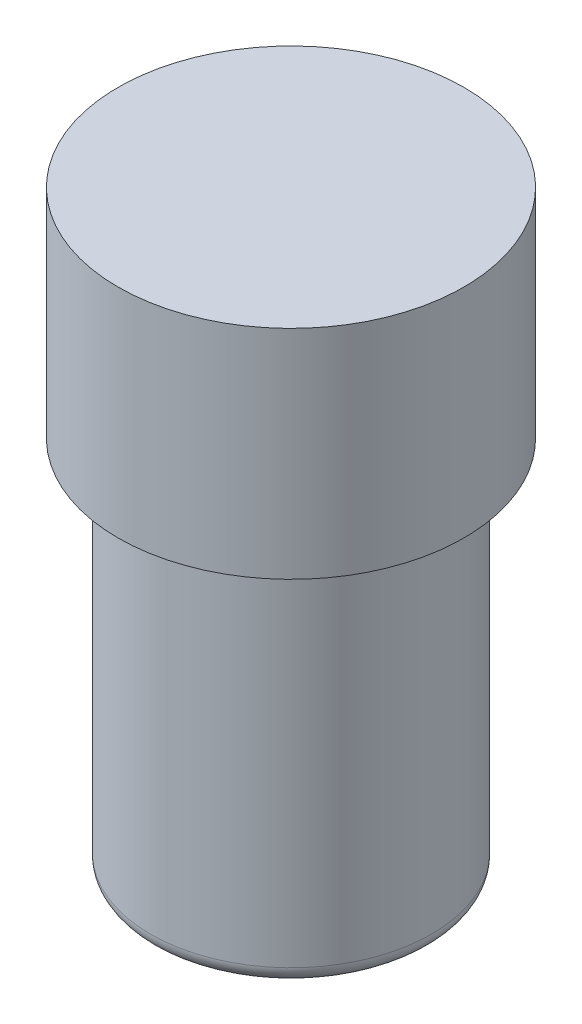
SolidWorks part; units mm, degrees
ref_plane "Front Plane" through (0, 0, 0) normal (0, 0, 1) x (1, 0, 0)
ref_plane "Top Plane" through (0, 0, 0) normal (0, 1, 0) x (1, 0, 0)
ref_plane "Right Plane" through (0, 0, 0) normal (1, 0, 0) x (0, 0, -1)
sketch "Sketch1" plane through (0, 0, 0) normal (0, 1, 0) x (1, 0, 0)
  circle A0 centre (0, 0) radius 5.0535
  circle A1 centre (0, 0) radius 4.1047
  dimension "D1" = 10.107
  dimension "D2" = 8.2094
extrude "Boss-Extrude1" add sketch "Sketch1" along normal blind 6.35 contours A1 | A0 A1 region at (-4.9106, 0, 0) region at (0, 0, 0)
extrude "Boss-Extrude2" add sketch "Sketch1<3>" against normal blind 11 contours A1 region at (0, 0, 0)
sketch "Sketch1<3>" plane through (0, 0, 0) normal (0, 1, 0) x (1, 0, 0) same geometry as "Sketch1"
fillet "Fillet2" radius 0.5 2 edges at (0, 0, 4.1047) (0, -11, 4.1047)
equation "\"outside_d\"=10.033"
equation "\"D1@Sketch1\"=\"outside_d\"+0.124-0.05"
equation "\"inside_d\"=7.9756"
equation "\"D2@Sketch1\"=\"inside_d\" + 0.2838-0.05"
